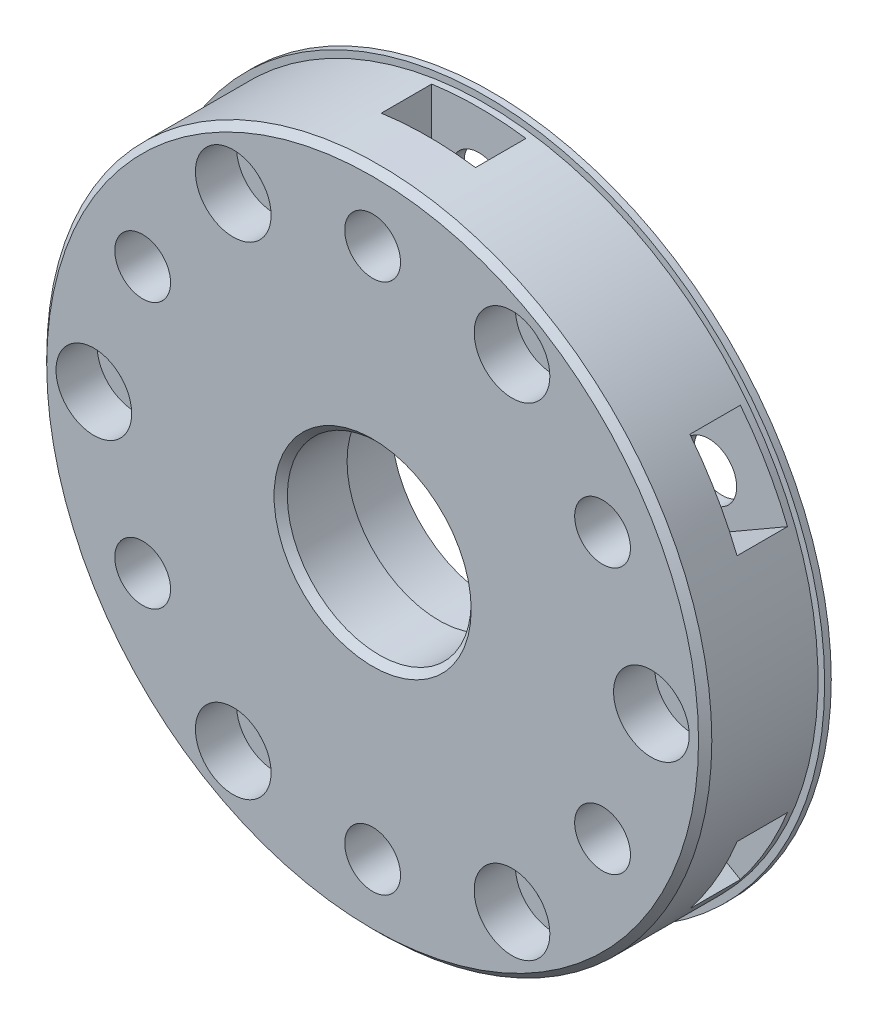
SolidWorks part; units mm, degrees
material "ABS"
ref_plane "Front Plane" through (0, 0, 0) normal (0, 0, 1) x (1, 0, 0)
ref_plane "Top Plane" through (0, 0, 0) normal (0, 1, 0) x (1, 0, 0)
ref_plane "Right Plane" through (0, 0, 0) normal (1, 0, 0) x (0, 0, -1)
sketch "Output Master Sketch" plane through (0, 0, 0) normal (0, 0, 1) x (1, 0, 0)
  circle A0 centre (0, 0) radius 21 construction
  circle A1 centre (21, 0) radius 2.85 construction
  circle A2 centre (10.5, -18.1865) radius 2.85 construction
  circle A3 centre (-10.5, -18.1865) radius 2.85 construction
  circle A4 centre (-21, 0) radius 2.85 construction
  circle A5 centre (-10.5, 18.1865) radius 2.85 construction
  circle A6 centre (10.5, 18.1865) radius 2.85 construction
  circle A7 centre (0, 0) radius 25.05
  point P17 (0, 0)
extrude "Boss-Extrude1" add sketch "Output Master Sketch" along normal blind 9
sketch "Sketch4" plane through (0, 0, 0) normal (0, 0, 1) x (1, 0, 0)
  circle A0 centre (21, 0) radius 2.85
  circle A1 centre (21, 0) radius 2.85 construction
  circle A2 centre (10.5, -18.1865) radius 2.85
  circle A3 centre (-10.5, -18.1865) radius 2.85
  circle A4 centre (-21, 0) radius 2.85
  circle A5 centre (-10.5, 18.1865) radius 2.85
  circle A6 centre (10.5, 18.1865) radius 2.85
  point P17 (0, 0)
  dimension "D1" = 6
extrude "Cut-Extrude1" cut sketch "Sketch4" along normal blind 4
sketch "Sketch5" plane through (0, 0, 0) normal (0, 0, -1) x (-1, 0, 0)
  circle A0 centre (0, 0) radius 25.05
  circle A1 centre (0, 0) radius 25.55
  circle A2 centre (0, 0) radius 25.05 construction
  dimension "D1" = 0.5
extrude "Boss-Extrude2" add sketch "Sketch5" against normal blind 0.5
sketch "Sketch6" plane through (0, 0, 0) normal (0, 0, -1) x (-1, 0, 0)
  circle A0 centre (-21, 0) radius 1.55
  circle A1 centre (-10.5, 18.1865) radius 1.55
  circle A2 centre (10.5, 18.1865) radius 1.55
  circle A3 centre (21, 0) radius 1.55
  circle A4 centre (10.5, -18.1865) radius 1.55
  circle A5 centre (-10.5, -18.1865) radius 1.55
  point P15 (0, 0)
  dimension "D1" = 3.1
  dimension "D2" = 6
extrude "Cut-Extrude2" cut sketch "Sketch6" against normal through all
sketch "Sketch7" plane through (0, 0, 9) normal (0, 0, 1) x (1, 0, 0)
  circle A0 centre (-21, 0) radius 2.85
  circle A1 centre (-10.5, 18.1865) radius 2.85
  circle A2 centre (10.5, 18.1865) radius 2.85
  circle A3 centre (21, 0) radius 2.85
  circle A4 centre (10.5, -18.1865) radius 2.85
  circle A5 centre (-10.5, -18.1865) radius 2.85
  point P16 (0, 0)
  dimension "D1" = 5.7
  dimension "D2" = 6
extrude "Cut-Extrude3" cut sketch "Sketch7" against normal blind 3.1
chamfer "Chamfer1" distance 0.5 angle 45 1 edges at (25.05, 0, 9)
sketch "Sketch8" plane through (0, 0, 0) normal (0, 0, -1) x (-1, 0, 0)
  circle A0 centre (0, 0) radius 6.925
  dimension "D1" = 13.85
extrude "Cut-Extrude4" cut sketch "Sketch8" against normal blind 10
sketch "Sketch9" plane through (0, 0, 0) normal (0, 0, -1) x (-1, 0, 0)
  circle A0 centre (0, 0) radius 7.575
  dimension "D1" = 15.15
extrude "Cut-Extrude5" cut sketch "Sketch9" against normal blind 4
sketch "Sketch10" plane through (0, 0, 9) normal (0, 0, 1) x (1, 0, 0)
  line L1 (0, 20) -> (-17.3205, 10) construction
  line L2 (-17.3205, 10) -> (-17.3205, -10) construction
  line L3 (-17.3205, -10) -> (0, -20) construction
  line L4 (0, -20) -> (17.3205, -10) construction
  line L5 (17.3205, -10) -> (17.3205, 10) construction
  line L6 (17.3205, 10) -> (0, 20) construction
  circle A0 centre (0, 0) radius 20 construction
  circle A1 centre (0, 20) radius 2.1
  circle A2 centre (17.3205, 10) radius 2.1
  circle A3 centre (17.3205, -10) radius 2.1
  circle A4 centre (0, -20) radius 2.1
  circle A5 centre (-17.3205, -10) radius 2.1
  circle A6 centre (-17.3205, 10) radius 2.1
  point P22 (0, 0)
  dimension "D1" = 40
  dimension "D2" = 4.2
  dimension "D3" = 6
extrude "M4 Thru" cut sketch "Sketch10" against normal through all
chamfer "Chamfer3" distance 0.5 angle 45 1 edges at (6.925, 0, 9)
sketch "Sketch11" plane through (0, 0, 9) normal (0, 0, 1) x (1, 0, 0)
  line L1 (0, 24.0992) -> (-3.55, 22.0496)
  line L2 (-3.55, 22.0496) -> (-3.55, 17.9504)
  line L3 (-3.55, 17.9504) -> (0, 15.9008)
  line L4 (0, 15.9008) -> (3.55, 17.9504)
  line L5 (3.55, 17.9504) -> (3.55, 22.0496)
  line L6 (3.55, 22.0496) -> (0, 24.0992)
  circle A0 centre (0, 20) radius 3.55 construction
  dimension "D1" = 7.1
extrude "M4 Hexnut Cut" cut sketch "Sketch11" along normal blind 3.8 from offset 8 offset against normal yes
ref_plane "Plane2" through (0, 22.0496, 0) normal (0, 1, 0) x (1, 0, 0)
sketch "Sketch12" plane through (0, 22.0496, 0) normal (0, 1, 0) x (1, 0, 0)
  line L1 (-3.55, -1) -> (3.55, -1)
  line L2 (-3.55, -1) -> (-3.55, -4.8)
  line L3 (-3.55, -4.8) -> (3.55, -4.8)
  line L4 (3.55, -1) -> (3.55, -4.8)
extrude "M4 Hexnut Slot" cut sketch "Sketch12" along normal through all contours L2 L1 L4 L3
pattern_circular "M4 Hexnut Pattern" count 6 over 360 about axis through (0, 0, 10) along (0, 0, -1) of "M4 Hexnut Cut", "M4 Hexnut Slot" reverse direction yes
